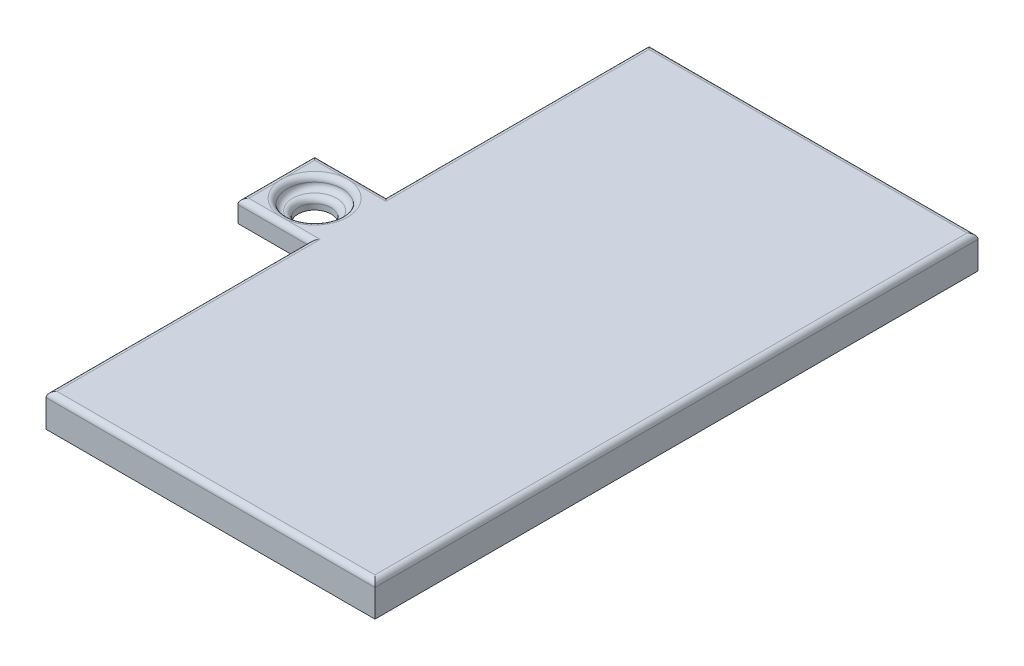
SolidWorks part; units mm, degrees
ref_plane "Front Plane" through (0, 0, 0) normal (0, 0, 1) x (1, 0, 0)
ref_plane "Top Plane" through (0, 0, 0) normal (0, 1, 0) x (1, 0, 0)
ref_plane "Right Plane" through (0, 0, 0) normal (1, 0, 0) x (0, 0, -1)
sketch "Sketch1" plane through (0, 0, 0) normal (0, 1, 0) x (1, 0, 0)
  line L1 (15, -27.5) -> (-15, -27.5)
  line L2 (15, -27.5) -> (15, 27.5)
  line L3 (15, 27.5) -> (-15, 27.5)
  line L4 (-15, -27.5) -> (-15, 27.5)
  line L5 (15, -27.5) -> (-15, 27.5) construction
  line L6 (15, 27.5) -> (-15, -27.5) construction
  point P0 (0, 0)
  dimension "D1" = 55
  dimension "D2" = 30
extrude "Boss-Extrude1" add sketch "Sketch1" along normal blind 3
sketch "Sketch2" plane through (0, 3, 0) normal (0, 1, 0) x (1, 0, 0)
  line L0 (-15, 27.5) -> (-15, -27.5) construction
  line L1 (-14.5, 3.5) -> (-21.5, 3.5)
  line L2 (-14.5, 3.5) -> (-14.5, -3.5)
  line L3 (-14.5, -3.5) -> (-21.5, -3.5)
  line L4 (-21.5, 3.5) -> (-21.5, -3.5)
  point P4 (-14.5, 0)
  point P6 (-21.5, 0)
  point P9 (-15, 0)
  dimension "D1" = 7
  dimension "D2" = 7
  dimension "D3" = 27.5
  dimension "D4" = 6.5
extrude "Boss-Extrude2" add sketch "Sketch2" against normal blind 2
sketch "Sketch3" plane through (0, 3, 0) normal (0, 1, 0) x (1, 0, 0)
  circle A0 centre (-18, 0) radius 1.5
  dimension "D1" = 33
extrude "Cut-Extrude1" cut sketch "Sketch3" against normal blind 2
sketch "Sketch4" plane through (0, 3, 0) normal (0, 1, 0) x (1, 0, 0)
  circle A0 centre (-18, 0) radius 2.5
  dimension "D1" = 5
extrude "Cut-Extrude2" cut sketch "Sketch4" against normal blind 1
fillet "Fillet2" radius 0.5 11 edges at (-18, 2, 1.5) (-18, 2, 2.5) (0, 3, -27.5) (15, 3, 0) (0, 3, 27.5) (-15, 3, 15.5) (-18.25, 3, 3.5) (-21.5, 3, 0) (-18.25, 3, -3.5) (-15, 3, -15.5) (-18, 3, 2.5)
